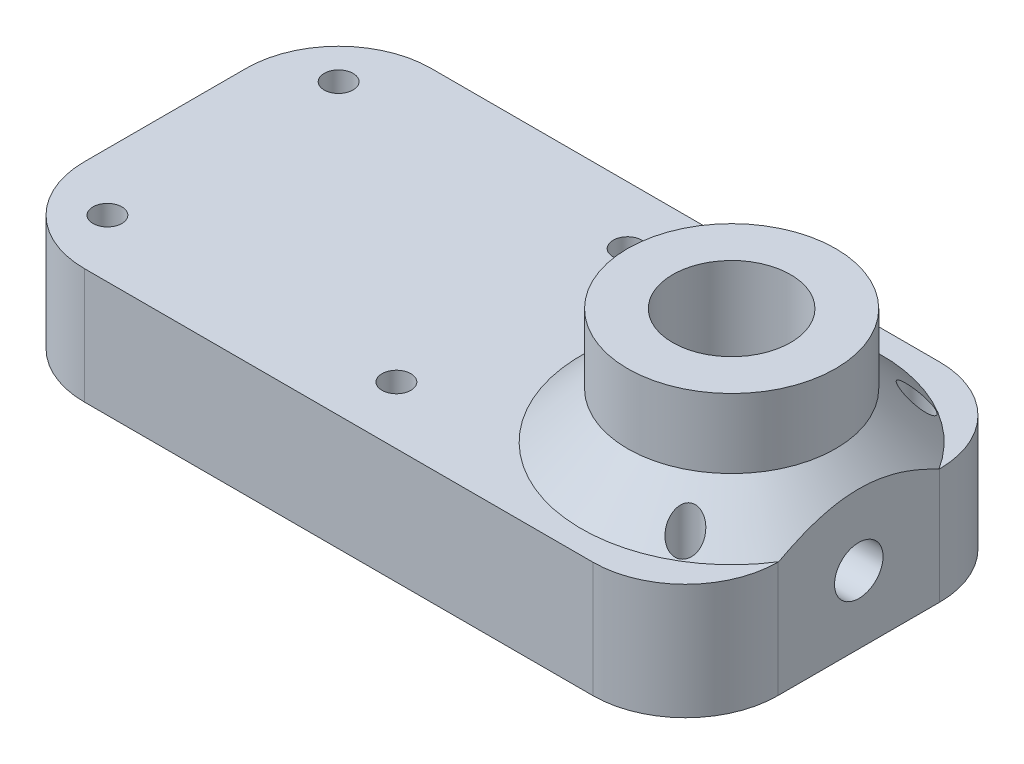
SolidWorks part; units mm, degrees
ref_plane "Front Plane" through (0, 0, 0) normal (0, 0, 1) x (1, 0, 0)
ref_plane "Top Plane" through (0, 0, 0) normal (0, 1, 0) x (1, 0, 0)
ref_plane "Right Plane" through (0, 0, 0) normal (1, 0, 0) x (0, 0, -1)
sketch "Sketch1" plane through (0, 0, 0) normal (0, 1, 0) x (1, 0, 0)
  line L1 (-49, 15) -> (11, 15)
  line L2 (-49, 15) -> (-49, -15)
  line L3 (-49, -15) -> (11, -15)
  line L4 (11, 15) -> (11, -15)
  circle A1 centre (0, 0) radius 9
  point P8 (11, 0)
  dimension "D2" = 18
  dimension "D3" = 30
  dimension "D4" = 60
  dimension "D1" = 11
extrude "Base" add sketch "Sketch1" along normal blind 10 contours L4 A1 L1 L2 L3 | A1 region at (-22.1283, 0, 0) region at (0, 0, 0)
fillet "AddALittleBeauty" radius 8 4 edges at (-49, 5, 15) (-49, 5, -15) (11, 5, -15) (11, 5, 15)
extrude "RodHolder" add sketch "Sketch1<3>" along normal blind 20 contours A1 region at (0, 0, 0)
sketch "Sketch1<3>" plane through (0, 0, 0) normal (0, 1, 0) x (1, 0, 0) same geometry as "Sketch1"
hole_wizard "M5x0.8 Tapped Hole for fixing rod" positions "Sketch3" profile "Sketch4" tap size "M5x0.8" standard "ANSI Metric"
sketch "Sketch3" plane through (11, 0, 0) normal (1, 0, 0) x (0, 0, -1)
  point P0 (0, 5.8799)
cosmetic thread "Hole Thread1" parameters "D1"=6.3524, "D2"=5
sketch "Sketch4" plane through (11, 5.8799, 0) normal (0, 1, 0) x (0, 0, -1)
  line L0 (0, 0) -> (0, 11.6618)
  line L1 (0, 11.6618) -> (2.1, 10.4)
  line L2 (2.1, 10.4) -> (2.1, 0)
  line L5 (2.1, 0) -> (0, 0)
  line L10 (0, 11.6618) -> (-2.1, 10.4) construction
  line L11 (0, -6.35) -> (0, 107.95) construction
  dimension "Tap Drill Dia." = 4.2
  dimension "Tap Drill Depth" = 10.4
  dimension "Drill Angle" = 118
chamfer "Chamfer1" distance 4 angle 45 1 edges at (0, 10, 9)
hole_wizard "Ø10.2 (10.2) Rod Hole" positions "Sketch5" profile "Sketch6" hole size "Ø10.2" standard "ANSI Metric" end condition through all
sketch "Sketch5" plane through (0, 20, 0) normal (0, 1, 0) x (1, 0, 0)
  point P0 (0, 0)
sketch "Sketch6" plane through (0, 20, 0) normal (1, 0, 0) x (0, 0, 1)
  line L0 (0, 0) -> (0, 20)
  line L1 (0, 20) -> (5.1, 20)
  line L2 (5.1, 20) -> (5.1, 0)
  line L5 (5.1, 0) -> (0, 0)
  line L11 (0, -6.35) -> (0, 107.95) construction
  dimension "Thru Hole Dia." = 10.2
  dimension "Thru Hole Depth" = 20
hole_wizard "M3x0.5 Tapped Hole1" positions "Sketch7" profile "Sketch8" tap size "M3x0.5" standard "ANSI Metric" end condition through all
sketch "Sketch7" plane through (0, 0, 0) normal (0, -1, 0) x (-1, 0, 0)
  line L0 (41, 15) -> (-3, 15) construction
  line L1 (41, -15) -> (-3, -15) construction
  line L2 (49, 7) -> (49, -7) construction
  line L3 (-11, 7) -> (-11, -7) construction
  line L4 (19, 18.3865) -> (19, -17.1189) construction
  point P0 (-6, 10)
  point P3 (-6, -10)
  point P6 (44, -10)
  point P9 (44, 10)
  point P27 (19, 10)
  point P29 (19, -10)
  point P39 (19, 15)
  dimension "D1" = 5
  dimension "D2" = 5
  dimension "D3" = 5
  dimension "D4" = 5
sketch "Sketch8" plane through (6, 0, -10) normal (1, 0, 0) x (0, 0, -1)
  line L0 (0, 0) -> (0, 20)
  line L1 (0, 20) -> (1.25, 20)
  line L2 (1.25, 20) -> (1.25, 0.275)
  line L3 (1.25, 0.275) -> (1.525, 0)
  line L5 (1.525, 0) -> (0, 0)
  line L6 (-1.25, 0.275) -> (-1.525, 0) construction
  line L11 (0, -6.35) -> (0, 107.95) construction
  dimension "Thru Tap Drill Dia." = 2.5
  dimension "Thru Tap Drill Depth" = 20
  dimension "Near C'Sink Dia." = 3.05
  dimension "Near C'Sink Angle" = 90
cosmetic thread "Hole Thread2" parameters "D2"=3
cosmetic thread "Hole Thread3" parameters "D2"=3
cosmetic thread "Hole Thread4" parameters "D2"=3
cosmetic thread "Hole Thread5" parameters "D2"=3
cosmetic thread "Hole Thread6" parameters "D2"=3
cosmetic thread "Hole Thread7" parameters "D2"=3
equation "\"D2@Sketch1\"=10.00mm+8"
